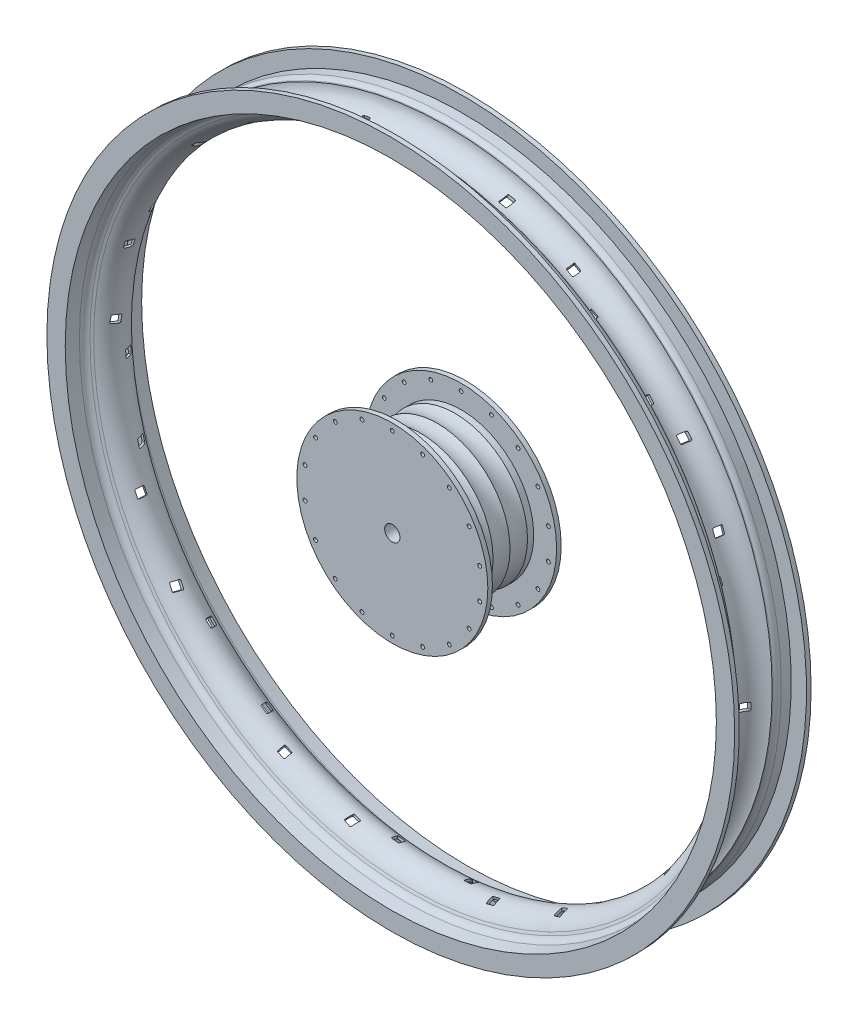
SolidWorks part; units mm, degrees
ref_plane "Спереди" through (0, 0, 0) normal (0, 0, 1) x (1, 0, 0)
ref_plane "Сверху" through (0, 0, 0) normal (0, 1, 0) x (1, 0, 0)
ref_plane "Справа" through (0, 0, 0) normal (1, 0, 0) x (0, 0, -1)
sketch "Эскиз1" plane through (0, 0, 0) normal (0, 0, 1) x (1, 0, 0)
  circle A0 centre (0, 0) radius 47.5
  dimension "D1" = 95
extrude "Бобышка-Вытянуть1" add sketch "Эскиз1" along normal mid plane 42
sketch "Эскиз3" plane through (0, 0, 0) normal (1, 0, 0) x (0, 0, -1)
  line L0 (-18.724, 0) -> (37.7483, 0) construction
  arc A0 (-5.5533, 47.4635) -> (5.5533, 47.4635) centre (0, 61.3977) ccw
  arc A1 (5.5533, 47.4635) -> (5.648, 75.2937) centre (11.2014, 61.3596) ccw
  arc A2 (-5.5533, 47.4635) -> (-5.648, 75.2937) centre (-11.2014, 61.3596) cw
  arc A3 (5.648, 75.2937) -> (-5.648, 75.2937) centre (0, 61.3977) ccw
  point P5 (5.5533, 47.4635)
  point P6 (5.5533, 47.4635)
  dimension "D1" = 30
  dimension "D2" = 30
revolve "Вырез-Повернуть1" cut sketch "Эскиз3" angle 360 about L0
sketch "Эскиз4" plane through (0, 0, 21) normal (0, 0, 1) x (1, 0, 0)
  circle A0 centre (0, 0) radius 5
  dimension "D1" = 10
extrude "Вырез-Вытянуть1" cut sketch "Эскиз4" against normal blind 42
sketch "Эскиз5" plane through (0, 0, 21) normal (0, 0, 1) x (1, 0, 0)
  circle A0 centre (0, 0) radius 62.5
  circle A1 centre (0, 0) radius 5
  dimension "D1" = 125
extrude "Бобышка-Вытянуть3" add sketch "Эскиз5" along normal blind 3
sketch "Эскиз8" plane through (0, 0, 24) normal (0, 0, 1) x (1, 0, 0)
  circle A0 centre (0, 58) radius 1.25
  circle A1 centre (19.8372, 54.5022) radius 1.25
  circle A2 centre (37.2817, 44.4306) radius 1.25
  circle A3 centre (50.2295, 29) radius 1.25
  circle A4 centre (57.1188, 10.0716) radius 1.25
  circle A5 centre (57.1188, -10.0716) radius 1.25
  circle A6 centre (50.2295, -29) radius 1.25
  circle A7 centre (37.2817, -44.4306) radius 1.25
  circle A8 centre (19.8372, -54.5022) radius 1.25
  circle A9 centre (0, -58) radius 1.25
  circle A10 centre (-19.8372, -54.5022) radius 1.25
  circle A11 centre (-37.2817, -44.4306) radius 1.25
  circle A12 centre (-50.2295, -29) radius 1.25
  circle A13 centre (-57.1188, -10.0716) radius 1.25
  circle A14 centre (-57.1188, 10.0716) radius 1.25
  circle A15 centre (-50.2295, 29) radius 1.25
  circle A16 centre (-37.2817, 44.4306) radius 1.25
  circle A17 centre (-19.8372, 54.5022) radius 1.25
  point P40 (0, 0)
  dimension "D1" = 2.5
  dimension "D2" = 58
  dimension "D3" = 18
extrude "Вырез-Вытянуть3" cut sketch "Эскиз8" against normal blind 3
mirror "Зеркальное отражение3" about plane through (0, 0, 0) normal (0, 0, 1) of "Вырез-Вытянуть3", "Бобышка-Вытянуть3"
sketch "Эскиз9" plane through (0, 0, 0) normal (0, 0, 1) x (1, 0, 0)
  circle A0 centre (0, 0) radius 225
  circle A1 centre (0, 0) radius 213
  dimension "D1" = 450
  dimension "D2" = 426
extrude "Бобышка-Вытянуть4" add sketch "Эскиз9" along normal mid plane 50 separate body
sketch "Эскиз10" plane through (0, 0, 0) normal (0, 1, 0) x (1, 0, 0)
  line L0 (0, 30.5135) -> (0, -30.7758) construction
  line L1 (-213, 25) -> (-213, -25)
  line L2 (-213, 25) -> (-212.1148, 16.5952)
  line L3 (-213, -25) -> (-212.1148, -16.5952)
  line L4 (-207.5655, -11.8096) -> (-209.2325, -12.5767)
  line L5 (-207.5655, 11.8096) -> (-209.2325, 12.5767)
  arc A0 (-207.5655, -11.8096) -> (-207.5655, 11.8096) centre (-213, 0) ccw
  arc A1 (-212.1148, 16.5952) -> (-209.2325, 12.5767) centre (-207.1423, 17.1188) ccw
  arc A2 (-212.1148, -16.5952) -> (-209.2325, -12.5767) centre (-207.1423, -17.1188) cw
  point P12 (-211.8169, 13.766)
  point P18 (-211.8169, -13.766)
  dimension "D2" = 5
revolve "Повернуть1" add sketch "Эскиз10" angle 360 about L0
sketch "Эскиз11" plane through (0, 0, 0) normal (0, 1, 0) x (1, 0, 0)
  line L0 (-225, 22) -> (-215, 22)
  line L1 (-225, 25) -> (-225, -25) construction
  line L2 (-215, 22) -> (-215, 15.5299)
  line L3 (-213.3625, 11.8294) -> (-213, 11.5)
  line L4 (-215, -22) -> (-215, -15.5299)
  line L5 (-225, -22) -> (-215, -22)
  line L6 (-225, 22) -> (-225, -22)
  line L7 (-213.3625, -11.8294) -> (-213, -11.5)
  line L8 (0, 37.1085) -> (0, -40.285) construction
  arc A0 (-213, -11.5) -> (-213, 11.5) centre (-213, 0) ccw
  arc A1 (-215, 15.5299) -> (-213.3625, 11.8294) centre (-210, 15.5299) ccw
  arc A2 (-213.3625, -11.8294) -> (-215, -15.5299) centre (-210, -15.5299) ccw
  dimension "D2" = 23
  dimension "D3" = 5
  dimension "D4" = 5
  dimension "D1" = 10
revolve "Вырез-Повернуть2" cut sketch "Эскиз11" angle 360 about L8
sketch "Эскиз12" plane through (0, 0, 24) normal (0, 0, 1) x (1, 0, 0)
  circle A0 centre (0, 58) radius 1.25
ref_plane "Плоскость1" through (0, 0, 4) normal (0, 0, 1) x (1, 0, 0)
sketch "Эскиз17" plane through (0, 0, 0) normal (1, 0, 0) x (0, 0, -1)
  line L0 (-27, 58) -> (25, 58) construction
  line L1 (-24, 59.25) -> (-24, 56.75) construction
  line L2 (25, -225) -> (25, 225) construction
  point P2 (-24, 58)
  point P8 (18, 58)
  dimension "D1" = 3
  dimension "D2" = 7
sketch "Эскиз18" plane through (0, 0, 4) normal (0, 0, 1) x (1, 0, 0)
  line L0 (0, 58) -> (-109.416, 167.416) construction
  line L1 (0, 58) -> (109.416, 167.416) construction
  circle A0 centre (0, 0) radius 200
sketch3d "Трехмерный эскиз2"
  line L2 (-109.416, 167.416, 4) -> (-58.6442, 116.6442, 14.6726)
  line L3 (109.416, 167.416, 4) -> (54.708, 112.708, -7)
ref_plane "Плоскость3" through (-58.6442, 116.6442, 14.6726) normal (0.6994, -0.6994, 0.147) x (0.104, -0.104, -0.9891)
sketch "Эскиз19" plane through (-58.6442, 116.6442, 14.6726) normal (0.6994, -0.6994, 0.147) x (0.104, -0.104, -0.9891)
  line L1 (-2, -2.5) -> (2, -2.5)
  line L2 (-2.5, -2) -> (-2.5, 2)
  line L3 (-2, 2.5) -> (2, 2.5)
  line L4 (2.5, -2) -> (2.5, 2)
  line L5 (-2.5, -2.5) -> (2.5, 2.5) construction
  line L6 (-2.5, 2.5) -> (2.5, -2.5) construction
  arc A0 (2, 2.5) -> (2.5, 2) centre (2, 2) cw
  arc A1 (2.5, -2) -> (2, -2.5) centre (2, -2) cw
  arc A2 (-2.5, -2) -> (-2, -2.5) centre (-2, -2) ccw
  arc A3 (-2.5, 2) -> (-2, 2.5) centre (-2, 2) cw
  point P0 (0, 0)
  dimension "D3" = 0.5
  dimension "D1" = 5
  dimension "D2" = 5
extrude "Вырез-Вытянуть5" cut sketch "Эскиз19" against normal blind 100
ref_plane "Плоскость4" through (54.708, 112.708, -7) normal (-0.7001, -0.7001, -0.1408) x (-0.7141, 0.6863, 0.138)
sketch "Эскиз20" plane through (54.708, 112.708, -7) normal (-0.7001, -0.7001, -0.1408) x (-0.7141, 0.6863, 0.138)
  line L1 (-2, -2.5) -> (2, -2.5)
  line L2 (-2.5, -2) -> (-2.5, 2)
  line L3 (-2, 2.5) -> (2, 2.5)
  line L4 (2.5, -2) -> (2.5, 2)
  line L5 (-2.5, -2.5) -> (2.5, 2.5) construction
  line L6 (-2.5, 2.5) -> (2.5, -2.5) construction
  arc A0 (2, 2.5) -> (2.5, 2) centre (2, 2) cw
  arc A1 (2.5, -2) -> (2, -2.5) centre (2, -2) cw
  arc A2 (-2, -2.5) -> (-2.5, -2) centre (-2, -2) cw
  arc A3 (-2.5, 2) -> (-2, 2.5) centre (-2, 2) cw
  point P0 (0, 0)
  dimension "D3" = 0.5
  dimension "D1" = 5
  dimension "D2" = 5
extrude "Вырез-Вытянуть6" cut sketch "Эскиз20" against normal blind 100
ref_plane "Плоскость5" through (0, 0, -4) normal (0, 0, 1) x (1, 0, 0)
sketch "Эскиз21" plane through (0, 0, -4) normal (0, 0, 1) x (1, 0, 0)
  line L0 (0, 0) -> (19.8372, 54.5022) construction
  line L1 (19.8372, 54.5022) -> (37.337, 48.1327) construction
  line L2 (19.8372, 54.5022) -> (42.7212, 65.1732) construction
  line L3 (19.8372, 54.5022) -> (-25.6798, 152.1136) construction
  line L4 (-25.6798, 152.1136) -> (-45.5578, 194.7421) construction
  line L5 (42.7212, 65.1732) -> (160.0771, 119.8971) construction
  circle A0 centre (0, 0) radius 200
  dimension "D2" = 45
  dimension "D1" = 45
sketch "Эскиз22" plane through (0, 0, -24) normal (0, 0, -1) x (-1, 0, 0)
  circle A0 centre (-19.8372, 54.5022) radius 1.25
sketch "Эскиз23" plane through (0, 0, 0) normal (1, 0, 0) x (0, 0, -1)
  line L0 (27, 54.5022) -> (-25, 54.5022) construction
  line L1 (-25, 225) -> (-25, -225) construction
  line L2 (24, 53.2522) -> (24, 55.7522) construction
  point P4 (24, 54.5022)
  point P5 (-18, 54.5022)
  dimension "D1" = 3
  dimension "D2" = 7
ref_plane "Плоскость6" through (19.8372, 0, 0) normal (1, 0, 0) x (0, 0, -1)
sketch "Эскиз24" plane through (19.8372, 0, 0) normal (1, 0, 0) x (0, 0, -1)
  line L0 (-25, 54.5022) -> (27, 54.5022) construction
  point P4 (-18, 54.5022)
sketch3d "Трехмерный эскиз4"
  line L0 (160.0771, 119.8971, -4) -> (103.2791, 93.4118, 4.9101)
  line L1 (-45.5578, 194.7421, -4) -> (-23.1125, 146.608, -11.8942)
  line L3 (160.0771, 119.8971, -4) -> (103.2791, 93.4118, 4.9101)
ref_plane "Плоскость7" through (103.2791, 93.4118, 4.9101) normal (-0.8973, -0.4184, 0.1408) x (0.1276, 0.0595, 0.99)
sketch "Эскиз25" plane through (103.2791, 93.4118, 4.9101) normal (-0.8973, -0.4184, 0.1408) x (0.1276, 0.0595, 0.99)
  line L1 (-2, -2.5) -> (2, -2.5)
  line L2 (-2.5, -2) -> (-2.5, 2)
  line L3 (-2, 2.5) -> (2, 2.5)
  line L4 (2.5, -2) -> (2.5, 2)
  line L5 (-2.5, -2.5) -> (2.5, 2.5) construction
  line L6 (-2.5, 2.5) -> (2.5, -2.5) construction
  arc A0 (2, 2.5) -> (2.5, 2) centre (2, 2) cw
  arc A1 (2.5, -2) -> (2, -2.5) centre (2, -2) cw
  arc A2 (-2, -2.5) -> (-2.5, -2) centre (-2, -2) cw
  arc A3 (-2.5, 2) -> (-2, 2.5) centre (-2, 2) cw
  point P0 (0, 0)
  dimension "D3" = 0.5
  dimension "D1" = 5
  dimension "D2" = 5
extrude "Вырез-Вытянуть7" cut sketch "Эскиз25" against normal blind 97
ref_plane "Плоскость8" through (-23.1125, 146.608, -11.8942) normal (0.418, -0.8965, -0.147) x (-0.9084, -0.4125, -0.0677)
sketch "Эскиз26" plane through (-23.1125, 146.608, -11.8942) normal (0.418, -0.8965, -0.147) x (-0.9084, -0.4125, -0.0677)
  line L1 (-2, -2.5) -> (2, -2.5)
  line L2 (-2.5, -2) -> (-2.5, 2)
  line L3 (-2, 2.5) -> (2, 2.5)
  line L4 (2.5, -2) -> (2.5, 2)
  line L5 (-2.5, -2.5) -> (2.5, 2.5) construction
  line L6 (-2.5, 2.5) -> (2.5, -2.5) construction
  arc A0 (2, 2.5) -> (2.5, 2) centre (2, 2) cw
  arc A1 (2.5, -2) -> (2, -2.5) centre (2, -2) cw
  arc A2 (-2, -2.5) -> (-2.5, -2) centre (-2, -2) cw
  arc A3 (-2.5, 2) -> (-2, 2.5) centre (-2, 2) cw
  point P0 (0, 0)
  dimension "D3" = 0.5
  dimension "D1" = 5
  dimension "D2" = 5
extrude "Вырез-Вытянуть8" cut sketch "Эскиз26" against normal blind 97
pattern_circular "Круговой массив1" count 9 every 40 about axis through (0, 0, -21) along (0, 0, 1) of "Вырез-Вытянуть5", "Вырез-Вытянуть6", "Вырез-Вытянуть7", "Вырез-Вытянуть8"
